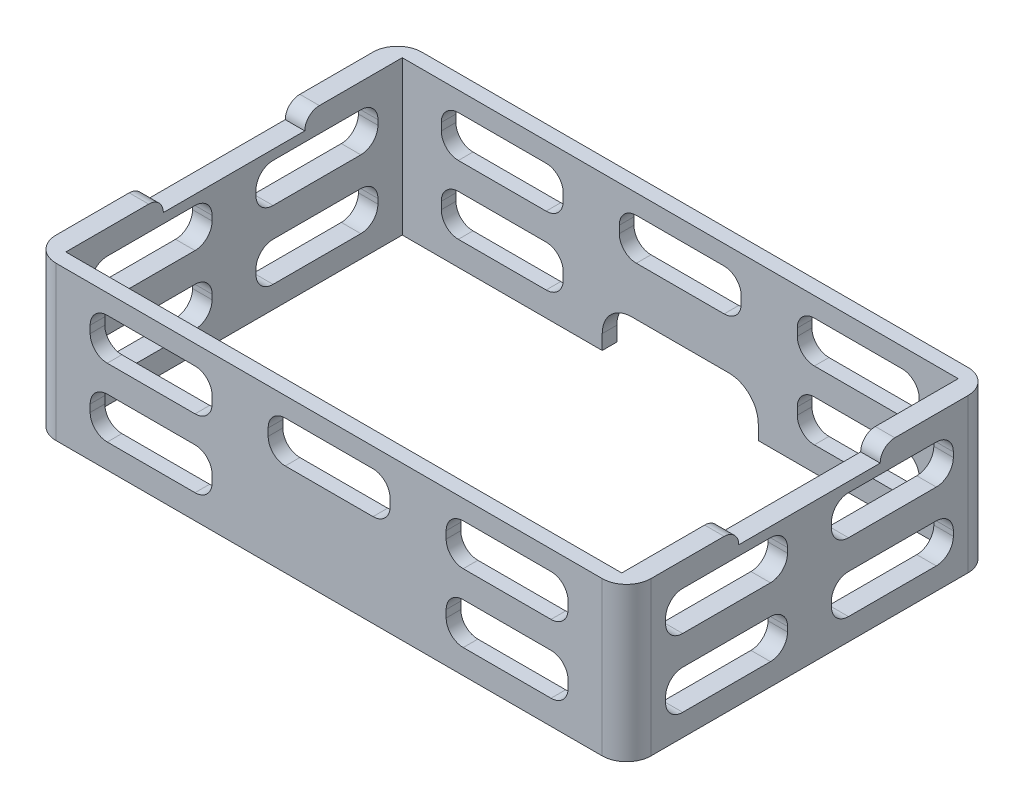
SolidWorks part; units mm, degrees
ref_plane "Front Plane" through (0, 0, 0) normal (0, 0, 1) x (1, 0, 0)
ref_plane "Top Plane" through (0, 0, 0) normal (0, 1, 0) x (1, 0, 0)
ref_plane "Right Plane" through (0, 0, 0) normal (1, 0, 0) x (0, 0, -1)
sketch "Sketch1" plane through (0, 0, 0) normal (0, 1, 0) x (1, 0, 0)
  line L1 (-120.1903, -82.0445) -> (-59.1903, -82.0445)
  line L2 (-120.1903, -82.0445) -> (-120.1903, -44.5445)
  line L3 (-120.1903, -44.5445) -> (-59.1903, -44.5445)
  line L4 (-59.1903, -82.0445) -> (-59.1903, -44.5445)
  dimension "D1" = 61
  dimension "D2" = 37.5
extrude "Boss-Extrude1" add sketch "Sketch1" along normal blind 15.75
sketch "Sketch2" plane through (0, 15.75, 0) normal (0, 1, 0) x (1, 0, 0)
  line L0 (-59.1903, -82.0445) -> (-59.1903, -44.5445) construction
  line L1 (-118.1903, -46.0445) -> (-61.1903, -46.0445)
  line L2 (-118.1903, -46.0445) -> (-118.1903, -80.5445)
  line L3 (-118.1903, -80.5445) -> (-61.1903, -80.5445)
  line L4 (-61.1903, -46.0445) -> (-61.1903, -80.5445)
  line L6 (-120.1903, -82.0445) -> (-59.1903, -82.0445) construction
  dimension "D1" = 57
  dimension "D2" = 34.5
  dimension "D3" = 2
  dimension "D4" = 1.5
extrude "Cut-Extrude1" cut sketch "Sketch2" against normal blind 15.75
sketch "Sketch3" plane through (0, 15.75, 0) normal (0, 1, 0) x (1, 0, 0)
  line L0 (-120.1903, -44.5445) -> (-120.1903, -82.0445) construction
  line L1 (-120.1903, -56.0445) -> (-118.1903, -56.0445)
  line L2 (-120.1903, -56.0445) -> (-120.1903, -70.5445)
  line L3 (-120.1903, -70.5445) -> (-118.1903, -70.5445)
  line L4 (-118.1903, -56.0445) -> (-118.1903, -70.5445)
  line L5 (-118.1903, -46.0445) -> (-118.1903, -80.5445) construction
  line L6 (-61.1903, -46.0445) -> (-118.1903, -46.0445) construction
  line L7 (-118.1903, -80.5445) -> (-61.1903, -80.5445) construction
  line L8 (-61.1903, -80.5445) -> (-61.1903, -46.0445) construction
  line L9 (-61.1903, -56.0445) -> (-59.1903, -56.0445)
  line L10 (-61.1903, -56.0445) -> (-61.1903, -70.5445)
  line L11 (-61.1903, -70.5445) -> (-59.1903, -70.5445)
  line L12 (-59.1903, -56.0445) -> (-59.1903, -70.5445)
  line L13 (-59.1903, -82.0445) -> (-59.1903, -44.5445) construction
  dimension "D1" = 10
  dimension "D2" = 10
  dimension "D3" = 10
  dimension "D4" = 10
extrude "Cut-Extrude2" cut sketch "Sketch3" against normal blind 1.5
fillet "Fillet1" radius 1.5 1 edges at (-119.1903, 15.75, 56.0445) type face fillet first side face at (-119.1903, 15, 56.0445) second side face at (-89.6903, 15.75, 50.6695)
fillet "Fillet2" radius 1.5 1 edges at (-119.1903, 15.75, 70.5445) type face fillet first side face at (-119.1903, 15, 70.5445) second side face at (-89.6903, 15.75, 75.9195)
fillet "Fillet3" radius 1.5 1 edges at (-60.1903, 15.75, 70.5445) type face fillet first side face at (-60.1903, 15, 70.5445) second side face at (-89.6903, 15.75, 76.2945)
fillet "Fillet4" radius 1.5 1 edges at (-60.1903, 15.75, 56.0445) type face fillet first side face at (-60.1903, 15, 56.0445) second side face at (-89.6903, 15.75, 50.2945)
fillet "Fillet5" radius 2.5 1 edges at (-120.1903, 7.875, 82.0445) type face fillet first side face at (-120.1903, 11.5152, 63.2945) second side face at (-89.6903, 7.875, 82.0445)
fillet "Fillet6" radius 2.5 1 edges at (-120.1903, 7.875, 44.5445) type face fillet first side face at (-120.1903, 11.5152, 62.6695) second side face at (-89.6903, 7.875, 44.5445)
fillet "Fillet7" radius 2.5 1 edges at (-59.1903, 7.875, 44.5445) type face fillet first side face at (-88.4403, 7.875, 44.5445) second side face at (-59.1903, 11.5152, 63.2945)
fillet "Fillet8" radius 2.5 1 edges at (-59.1903, 7.875, 82.0445) type face fillet first side face at (-59.1903, 11.5152, 63.9195) second side face at (-88.4403, 7.875, 82.0445)
sketch "Sketch4" plane through (0, 0, 44.5445) normal (0, 0, -1) x (-1, 0, 0)
  line L0 (61.6903, 0) -> (117.6903, 0) construction
  line L1 (81.6903, 0) -> (97.6903, 0)
  line L2 (81.6903, 0) -> (81.6903, 4.5)
  line L3 (81.6903, 4.5) -> (97.6903, 4.5)
  line L4 (97.6903, 0) -> (97.6903, 4.5)
  dimension "D1" = 16
  dimension "D2" = 4.5
  dimension "D3" = 20.5
extrude "Cut-Extrude3" cut sketch "Sketch4" against normal blind 1.5
fillet "Fillet9" radius 3 1 edges at (-81.6903, 4.5, 45.2945) type face fillet first side face at (-81.6903, 2.25, 45.2945) second side face at (-89.6903, 4.5, 45.2945)
fillet "Fillet10" radius 3 1 edges at (-97.6903, 4.5, 45.2945) type face fillet first side face at (-97.6903, 2.25, 45.2945) second side face at (-91.1903, 4.5, 45.2945)
sketch "Sketch6" plane through (0, 0, 44.5445) normal (0, 0, -1) x (-1, 0, 0)
  line L0 (61.6903, 15.75) -> (117.6903, 15.75) construction
  line L1 (66.9403, 13.75) -> (75.9403, 13.75)
  line L2 (65.1903, 12) -> (65.1903, 11.25)
  line L3 (66.9403, 9.5) -> (75.9403, 9.5)
  line L4 (77.6903, 12) -> (77.6903, 11.25)
  line L5 (83.4403, 12) -> (83.4403, 11.25)
  line L6 (85.1903, 13.75) -> (94.1903, 13.75)
  line L7 (95.9403, 12) -> (95.9403, 11.25)
  line L8 (85.1903, 9.5) -> (94.1903, 9.5)
  line L9 (101.6903, 12) -> (101.6903, 11.25)
  line L10 (103.4403, 13.75) -> (112.4403, 13.75)
  line L11 (114.1903, 12) -> (114.1903, 11.25)
  line L12 (103.4403, 9.5) -> (112.4403, 9.5)
  line L17 (101.6903, 5) -> (101.6903, 4.25)
  line L18 (103.4403, 6.75) -> (112.4403, 6.75)
  line L19 (114.1903, 5) -> (114.1903, 4.25)
  line L20 (103.4403, 2.5) -> (112.4403, 2.5)
  line L21 (65.1903, 5) -> (65.1903, 4.25)
  line L22 (66.9403, 6.75) -> (75.9403, 6.75)
  line L23 (77.6903, 5) -> (77.6903, 4.25)
  line L24 (66.9403, 2.5) -> (75.9403, 2.5)
  line L25 (83.4403, 5) -> (83.4403, 4.25) [skipped]
  line L26 (85.1903, 2.5) -> (94.1903, 2.5) [skipped]
  line L27 (95.9403, 5) -> (95.9403, 4.25) [skipped]
  line L28 (85.1903, 6.75) -> (94.1903, 6.75) [skipped]
  arc A0 (65.1903, 11.25) -> (66.9403, 9.5) centre (66.9403, 11.25) ccw
  arc A1 (66.9403, 13.75) -> (65.1903, 12) centre (66.9403, 12) ccw
  arc A2 (75.9403, 13.75) -> (77.6903, 12) centre (75.9403, 12) cw
  arc A3 (75.9403, 9.5) -> (77.6903, 11.25) centre (75.9403, 11.25) ccw
  arc A4 (85.1903, 13.75) -> (83.4403, 12) centre (85.1903, 12) ccw
  arc A5 (83.4403, 11.25) -> (85.1903, 9.5) centre (85.1903, 11.25) ccw
  arc A6 (94.1903, 13.75) -> (95.9403, 12) centre (94.1903, 12) cw
  arc A7 (94.1903, 9.5) -> (95.9403, 11.25) centre (94.1903, 11.25) ccw
  arc A8 (103.4403, 13.75) -> (101.6903, 12) centre (103.4403, 12) ccw
  arc A9 (101.6903, 11.25) -> (103.4403, 9.5) centre (103.4403, 11.25) ccw
  arc A10 (112.4403, 13.75) -> (114.1903, 12) centre (112.4403, 12) cw
  arc A11 (112.4403, 9.5) -> (114.1903, 11.25) centre (112.4403, 11.25) ccw
  arc A16 (103.4403, 6.75) -> (101.6903, 5) centre (103.4403, 5) ccw
  arc A17 (101.6903, 4.25) -> (103.4403, 2.5) centre (103.4403, 4.25) ccw
  arc A18 (112.4403, 6.75) -> (114.1903, 5) centre (112.4403, 5) cw
  arc A19 (112.4403, 2.5) -> (114.1903, 4.25) centre (112.4403, 4.25) ccw
  arc A20 (66.9403, 6.75) -> (65.1903, 5) centre (66.9403, 5) ccw
  arc A21 (65.1903, 4.25) -> (66.9403, 2.5) centre (66.9403, 4.25) ccw
  arc A22 (75.9403, 6.75) -> (77.6903, 5) centre (75.9403, 5) cw
  arc A23 (75.9403, 2.5) -> (77.6903, 4.25) centre (75.9403, 4.25) ccw
  arc A24 (83.4403, 4.25) -> (85.1903, 2.5) centre (85.1903, 4.25) ccw [skipped]
  arc A25 (94.1903, 2.5) -> (95.9403, 4.25) centre (94.1903, 4.25) ccw [skipped]
  arc A26 (94.1903, 6.75) -> (95.9403, 5) centre (94.1903, 5) cw [skipped]
  arc A27 (85.1903, 6.75) -> (83.4403, 5) centre (85.1903, 5) ccw [skipped]
  point P4 (71.4403, 9.5)
  point P11 (65.1903, 9.5)
  point P14 (65.1903, 13.75)
  point P19 (77.6903, 9.5)
  dimension "D5" = 1.75
  dimension "D1" = 12.5
  dimension "D2" = 10.25
  dimension "D3" = 2
  dimension "D4" = 4.25
  dimension "D6" = 3
  dimension "D7" = 2
extrude "Cut-Extrude4" cut sketch "Sketch6" against normal blind 37.5
sketch "Sketch7" plane through (-120.1903, 0, 0) normal (-1, 0, 0) x (0, 0, 1)
  line L0 (47.0445, 15.75) -> (54.5445, 15.75) construction
  line L1 (50.2945, 13.25) -> (59.2945, 13.25)
  line L2 (48.5445, 11.5) -> (48.5445, 11)
  line L3 (50.2945, 9.25) -> (59.2945, 9.25)
  line L4 (61.0445, 11.5) -> (61.0445, 11)
  line L5 (65.5445, 11.5) -> (65.5445, 11)
  line L6 (67.2945, 13.25) -> (76.2945, 13.25)
  line L7 (78.0445, 11.5) -> (78.0445, 11)
  line L8 (67.2945, 9.25) -> (76.2945, 9.25)
  line L9 (65.5445, 4.5) -> (65.5445, 4)
  line L10 (67.2945, 6.25) -> (76.2945, 6.25)
  line L11 (78.0445, 4.5) -> (78.0445, 4)
  line L12 (67.2945, 2.25) -> (76.2945, 2.25)
  line L13 (48.5445, 4.5) -> (48.5445, 4)
  line L14 (50.2945, 6.25) -> (59.2945, 6.25)
  line L15 (61.0445, 4.5) -> (61.0445, 4)
  line L16 (50.2945, 2.25) -> (59.2945, 2.25)
  arc A0 (59.2945, 13.25) -> (61.0445, 11.5) centre (59.2945, 11.5) cw
  arc A1 (59.2945, 9.25) -> (61.0445, 11) centre (59.2945, 11) ccw
  arc A2 (48.5445, 11) -> (50.2945, 9.25) centre (50.2945, 11) ccw
  arc A3 (50.2945, 13.25) -> (48.5445, 11.5) centre (50.2945, 11.5) ccw
  arc A4 (67.2945, 13.25) -> (65.5445, 11.5) centre (67.2945, 11.5) ccw
  arc A5 (65.5445, 11) -> (67.2945, 9.25) centre (67.2945, 11) ccw
  arc A6 (76.2945, 13.25) -> (78.0445, 11.5) centre (76.2945, 11.5) cw
  arc A7 (76.2945, 9.25) -> (78.0445, 11) centre (76.2945, 11) ccw
  arc A8 (67.2945, 6.25) -> (65.5445, 4.5) centre (67.2945, 4.5) ccw
  arc A9 (65.5445, 4) -> (67.2945, 2.25) centre (67.2945, 4) ccw
  arc A10 (76.2945, 6.25) -> (78.0445, 4.5) centre (76.2945, 4.5) cw
  arc A11 (76.2945, 2.25) -> (78.0445, 4) centre (76.2945, 4) ccw
  arc A12 (50.2945, 6.25) -> (48.5445, 4.5) centre (50.2945, 4.5) ccw
  arc A13 (48.5445, 4) -> (50.2945, 2.25) centre (50.2945, 4) ccw
  arc A14 (59.2945, 6.25) -> (61.0445, 4.5) centre (59.2945, 4.5) cw
  arc A15 (59.2945, 2.25) -> (61.0445, 4) centre (59.2945, 4) ccw
  point P9 (61.0445, 13.25)
  point P12 (61.0445, 9.25)
  point P15 (48.5445, 9.25)
  dimension "D5" = 1.75
  dimension "D1" = 4
  dimension "D2" = 12.5
  dimension "D3" = 2.5
  dimension "D4" = 2.5
  dimension "D8" = 2.5
  dimension "D6" = 2
  dimension "D7" = 2
extrude "Cut-Extrude5" cut sketch "Sketch7" against normal blind 61
sketch "Sketch8" plane through (-120.1903, 0, 0) normal (-1, 0, 0) x (0, 0, 1)
  line L0 (47.0445, 0) -> (79.5445, 0) construction
  line L1 (49.5445, 0) -> (51.5445, 0)
  line L2 (49.5445, 0) -> (49.5445, -1)
  line L3 (49.5445, -1) -> (51.5445, -1)
  line L4 (51.5445, 0) -> (51.5445, -1)
  line L5 (44.5445, 0) -> (44.5445, 15.75) construction
  line L6 (75.0445, 0) -> (77.0445, 0)
  line L7 (75.0445, 0) -> (75.0445, -1)
  line L8 (75.0445, -1) -> (77.0445, -1)
  line L9 (77.0445, 0) -> (77.0445, -1)
  line L10 (82.0445, 15.75) -> (82.0445, 0) construction
  dimension "D1" = 5
  dimension "D2" = 5
  dimension "D3" = 2
  dimension "D4" = 2
  dimension "D5" = 1
  dimension "D6" = 1
